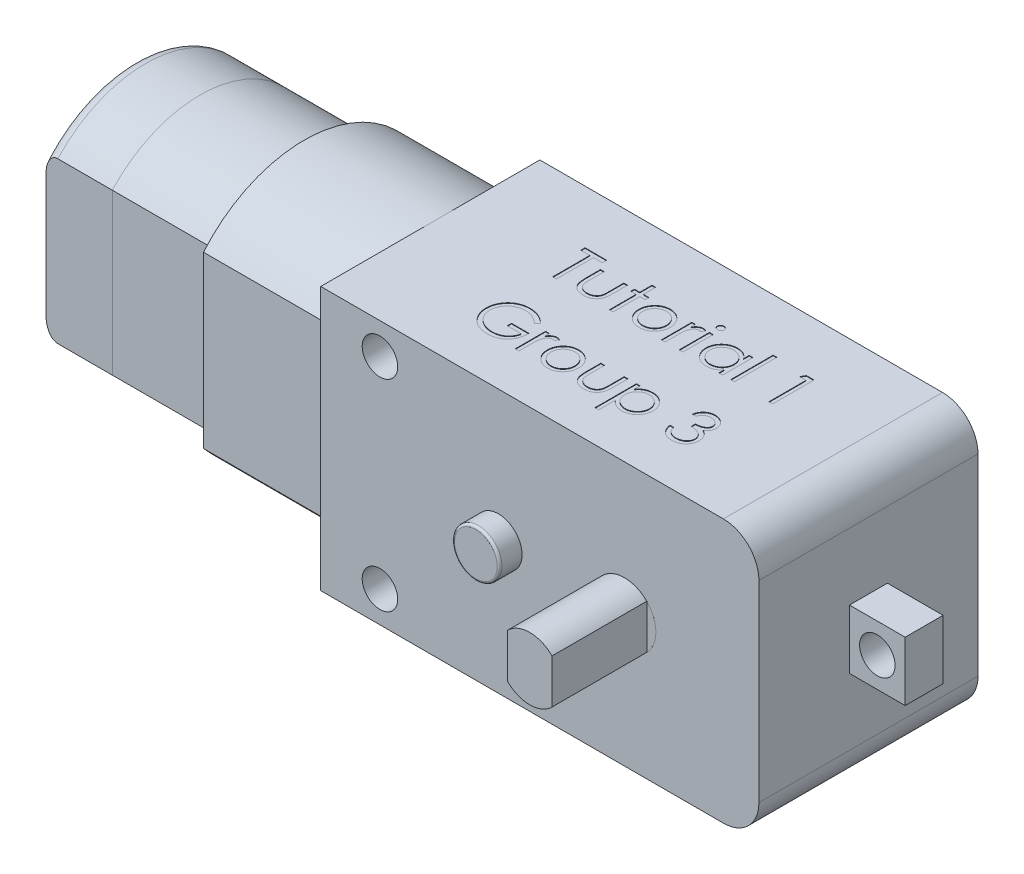
SolidWorks part; units mm, degrees
other "Markup1"
sketch "Sketch1" plane through (23.2, -11.125, 17.75) normal (0.3723, -0.0119, 0.928) x (0.9281, 0.003, -0.3723)
sketch "Sketch20" plane through (23.2, -11.125, 17.25) normal (0.3723, -0.0119, 0.928) x (0.9281, 0.003, -0.3723)
sketch "Sketch21" plane through (23.2, -11.125, 17.25) normal (0.3723, -0.0119, 0.928) x (0.9281, 0.003, -0.3723)
ref_plane "Front Plane" through (0, 0, 0) normal (0, 0, 1) x (1, 0, 0)
ref_plane "Top Plane" through (0, 0, 0) normal (0, 1, 0) x (1, 0, 0)
ref_plane "Right Plane" through (0, 0, 0) normal (1, 0, 0) x (0, 0, -1)
sketch "Sketch 1" plane through (0, 0, 0) normal (0, 0, 1) x (1, 0, 0)
  line L1 (-18.5, -11.125) -> (15.5, -11.125)
  line L2 (-18.5, -11.125) -> (-18.5, 11.125)
  line L3 (-18.5, 11.125) -> (15.5, 11.125)
  line L4 (18.5, -8.125) -> (18.5, 8.125)
  line L5 (-18.5, -11.125) -> (18.5, 11.125) construction
  line L6 (-18.5, 11.125) -> (18.5, -11.125) construction
  arc A0 (15.5, -11.125) -> (18.5, -8.125) centre (15.5, -8.125) ccw
  arc A1 (15.5, 11.125) -> (18.5, 8.125) centre (15.5, 8.125) cw
  point P0 (0, 0)
  dimension "D3" = 3
  dimension "D1" = 22.25
  dimension "D2" = 37
extrude "Boss-Extrude1" add sketch "Sketch 1" along normal blind 9.25 and the other way blind 9.25
sketch "Sketch2" plane through (-18.5, 0, 0) normal (-1, 0, 0) x (0, 0, 1)
  line L0 (-0.75, -11.125) -> (-0.75, 11.125) construction
  line L1 (7.75, -7.1774) -> (7.75, 7.1774)
  line L2 (-9.25, -7.1774) -> (-9.25, 7.1774)
  line L3 (9.25, 11.125) -> (9.25, -11.125) construction
  line L5 (7.75, -12.1318) -> (7.75, 11.125) construction
  line L6 (-9.25, -12.1318) -> (-9.25, 11.125) construction
  line L7 (-0.75, -12.1318) -> (-0.75, 11.125) construction
  arc A0 (7.75, 7.1774) -> (-9.25, 7.1774) centre (-0.75, 0) ccw
  arc A1 (-9.25, -7.1774) -> (7.75, -7.1774) centre (-0.75, 0) ccw
  point P8 (-0.75, 0)
  dimension "D1" = 22.25
  dimension "D2" = 8.5
  dimension "D3" = 8.5
  dimension "D4" = 1.5
extrude "Boss-Extrude2" add sketch "Sketch2" along normal blind 11.4
sketch "Sketch3" plane through (18.5, 0, 0) normal (1, 0, 0) x (0, 0, -1)
  line L1 (1.6, -2.5) -> (-1.6, -2.5)
  line L2 (1.6, -2.5) -> (1.6, 2.5)
  line L3 (1.6, 2.5) -> (-1.6, 2.5)
  line L4 (-1.6, -2.5) -> (-1.6, 2.5)
  line L5 (1.6, -2.5) -> (-1.6, 2.5) construction
  line L6 (1.6, 2.5) -> (-1.6, -2.5) construction
  point P0 (0, 0)
  dimension "D1" = 5
  dimension "D2" = 3.2
extrude "Boss-Extrude3" add sketch "Sketch3" along normal blind 4.7
sketch "Sketch4" plane through (0, 0, 0) normal (0, 0, 1) x (1, 0, 0)
  line L0 (0, 0) -> (-18.2045, 0) construction
  line L3 (-18.5, 11.125) -> (-18.5, -11.125) construction
  circle A0 centre (-13.5, 8.5) radius 1.5
  circle A1 centre (-13.5, -8.5) radius 1.5
  dimension "D1" = 3
  dimension "D2" = 17
  dimension "D5" = 5
extrude "Cut-Extrude1" cut sketch "Sketch4" against normal blind 17.7 and the other way blind 28
sketch "Sketch5" plane through (0, 0, 9.25) normal (0, 0, 1) x (1, 0, 0)
  line L0 (18.5, -8.125) -> (18.5, 8.125) construction
  circle A0 centre (-3.5, 0) radius 2
  point P6 (18.5, 0)
  dimension "D1" = 4
  dimension "D2" = 22
extrude "Boss-Extrude4" add sketch "Sketch5" along normal blind 1.9
fillet "Fillet1" radius 0.2 1 edges at (-1.5, 0, 11.15)
sketch "Sketch6" plane through (0, 0, 9.25) normal (0, 0, 1) x (1, 0, 0)
  line L0 (18.5, -8.125) -> (18.5, 8.125) construction
  circle A0 centre (7.15, 0) radius 2.65
  dimension "D1" = 5.3
  dimension "D2" = 11.35
extrude "Cut-Extrude2" cut sketch "Sketch6" against normal blind 23.9
sketch "Sketch9" plane through (-29.9, 0, 0) normal (-1, 0, 0) x (0, 0, 1)
  line L2 (6.65, -7.1774) -> (6.65, 7.1774)
  line L3 (6.65, -6.7632) -> (6.65, 6.7632)
  line L5 (-8.15, 7.1774) -> (-8.15, -7.1774)
  line L6 (-8.15, 6.7632) -> (-8.15, -6.7632)
  arc A2 (6.9096, 6.4678) -> (-8.4096, 6.4678) centre (-0.75, 0) ccw
  arc A3 (6.65, 6.7632) -> (-8.15, 6.7632) centre (-0.75, 0) ccw
  arc A5 (-8.4096, -6.4678) -> (6.9096, -6.4678) centre (-0.75, 0) ccw
  arc A6 (-8.15, -6.7632) -> (6.65, -6.7632) centre (-0.75, 0) ccw
  dimension "D1" = 1.1
  dimension "D2" = 1.1
  dimension "D3" = 1.1
  dimension "D4" = 1.1
extrude "Boss-Extrude5" add sketch "Sketch9" along normal blind 8.8 separate body
sketch "Sketch10" plane through (-38.7, 0, 0) normal (-1, 0, 0) x (0, 0, 1)
  line L0 (-8.15, 6.7632) -> (-8.15, -6.7632)
  line L1 (6.65, 6.7632) -> (6.65, -6.7632)
  line L2 (6.65, -6.7632) -> (6.65, 6.7632) construction
  arc A0 (6.65, 6.7632) -> (-8.15, 6.7632) centre (-0.75, 0) ccw
  arc A1 (6.65, 6.7632) -> (-8.15, 6.7632) centre (-0.75, 0) ccw construction
  arc A2 (-8.15, -6.7632) -> (6.65, -6.7632) centre (-0.75, 0) ccw
extrude "Boss-Extrude6" add sketch "Sketch10" along normal blind 5.6 separate body
fillet "Fillet2" radius 1 2 edges at (-44.3, 10.025, -0.75) (-44.3, -10.025, -0.75)
sketch "Sketch11" plane through (-44.3, 0, 0) normal (-1, 0, 0) x (0, 0, 1)
  line L0 (6.65, 5.1663) -> (6.65, -7.0924) construction
  line L1 (6.65, -6.7632) -> (6.65, -5.1663) construction
  line L2 (2.65, 3.6661) -> (2.65, -3.6661)
  line L3 (2.65, 5.1663) -> (2.65, -7.0924) construction
  arc A0 (2.65, 3.6661) -> (2.65, -3.6661) centre (-0.75, 0) ccw
  arc A2 (6.65, 6.7632) -> (-8.15, 6.7632) centre (-0.75, 0) ccw construction
  dimension "D1" = 10
  dimension "D2" = 4
extrude "Boss-Extrude7" add sketch "Sketch11" along normal blind 1 separate body
sketch "Sketch12" plane through (-45.3, 0, 0) normal (-1, 0, 0) x (0, 0, 1)
  circle A0 centre (-0.75, 0) radius 1
  arc A1 (2.65, 3.6661) -> (2.65, -3.6661) centre (-0.75, 0) ccw construction
  dimension "D1" = 2
extrude "Boss-Extrude8" add sketch "Sketch12" along normal blind 0.5 separate body
sketch "Sketch14" plane through (0, 0, 1.6) normal (0, 0, 1) x (1, 0, 0)
  line L0 (18.5, 2.5) -> (23.2, -2.5) construction
  line L1 (23.2, 2.5) -> (18.5, -2.5) construction
  circle A0 centre (20.85, 0) radius 1.5
  dimension "D1" = 3
extrude "Cut-Extrude3" cut sketch "Sketch14" against normal blind 4.2
sketch "Sketch15" plane through (0, 0, 0) normal (0, 0, 1) x (1, 0, 0)
  line L0 (7.15, -5.2054) -> (7.15, 5.2054) construction
  line L1 (9.03, -1.8676) -> (9.03, 1.8676)
  line L2 (5.27, -1.8676) -> (5.27, 1.8676)
  line L3 (9.03, -5.2054) -> (9.03, 5.2054) construction
  line L4 (5.27, -5.2054) -> (5.27, 5.2054) construction
  arc A0 (5.27, -1.8676) -> (9.03, -1.8676) centre (7.15, 0) ccw
  circle A1 centre (7.15, 0) radius 2.65 construction
  arc A2 (9.03, 1.8676) -> (5.27, 1.8676) centre (7.15, 0) ccw
  point P7 (7.15, 0)
  dimension "D1" = 3.76
extrude "Boss-Extrude10" add sketch "Sketch15" along normal blind 17.25 and the other way blind 17.25 separate body
sketch "Sketch16" plane through (0, 0, 0) normal (0, 0, 1) x (1, 0, 0)
  circle A0 centre (7.15, 0) radius 2.65
  circle A1 centre (7.15, 0) radius 2.65 construction
extrude "Boss-Extrude11" add sketch "Sketch16" along normal up to surface and the other way up to surface separate body up to face at (9.8, 0, 9.25) other way up to face at (4.5, 0, -9.25)
sketch "Sketch22" plane through (0, 11.125, 0) normal (0, 1, 0) x (1, 0, 0)
  text T0 "Tutorial 1\r\nGroup 3"
extrude "Cut-Extrude4" cut sketch "Sketch22" against normal blind 0.05
